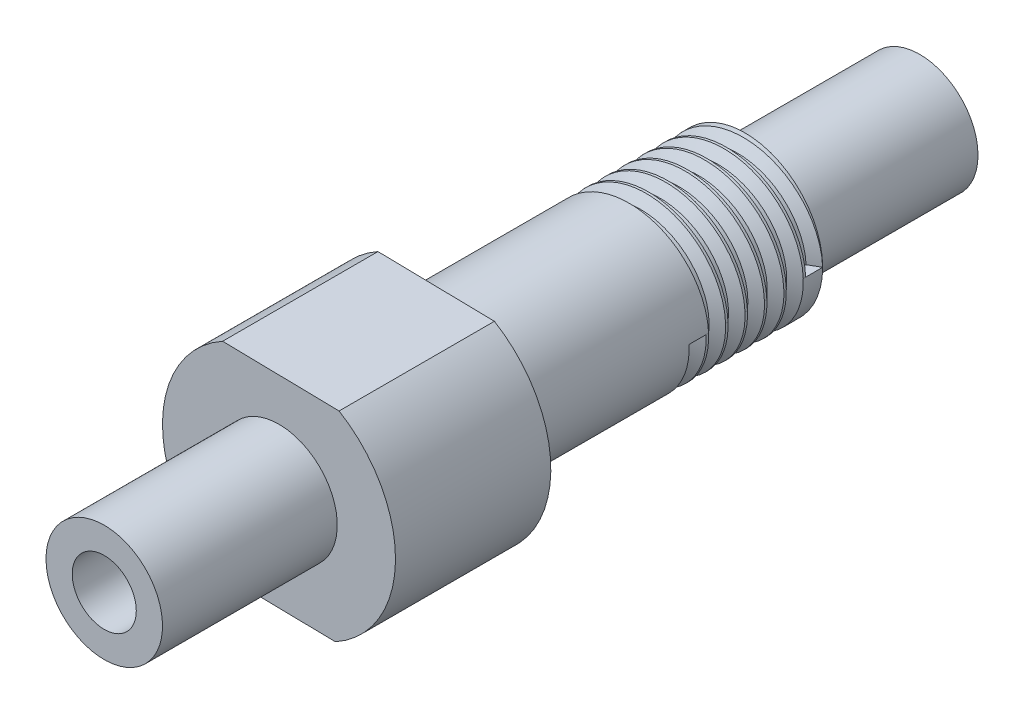
SolidWorks part; units mm, degrees
material "Stainless Steel (ferritic)"
ref_plane "Front Plane" through (0, 0, 0) normal (0, 0, 1) x (1, 0, 0)
ref_plane "Top Plane" through (0, 0, 0) normal (0, 1, 0) x (1, 0, 0)
ref_plane "Right Plane" through (0, 0, 0) normal (1, 0, 0) x (0, 0, -1)
sketch "Sketch1" plane through (0, 0, 0) normal (0, 0, 1) x (1, 0, 0)
  circle A0 centre (0, 0) radius 4
  dimension "D1" = 8
extrude "Boss-Extrude1" add sketch "Sketch1" along normal blind 16
sketch "Sketch2" plane through (0, 0, 16) normal (0, 0, 1) x (1, 0, 0)
  circle A0 centre (0, 0) radius 6
  dimension "D1" = 12
extrude "Boss-Extrude2" add sketch "Sketch2" along normal blind 8
sketch "Sketch3" plane through (0, 0, 0) normal (0, 0, -1) x (-1, 0, 0)
  circle A0 centre (0, 0) radius 3
  dimension "D1" = 6
extrude "Boss-Extrude3" add sketch "Sketch3" along normal blind 9
sketch "Sketch8" plane through (0, 0, 24) normal (0, 0, 1) x (1, 0, 0)
  circle A0 centre (0, 0) radius 3
  dimension "D1" = 6
extrude "Boss-Extrude4" add sketch "Sketch8" along normal blind 9
hole_wizard "M4x0.7 Tapped Hole2" positions "Sketch12" profile "Sketch13" tap size "M4x0.7" standard "ANSI Metric"
sketch "Sketch12" plane through (0, 0, 33) normal (0, 0, 1) x (1, 0, 0)
  point P0 (0, 0)
sketch "Sketch13" plane through (0, 0, 33) normal (1, 0, 0) x (0, -1, 0)
  line L0 (0, 0) -> (0, 10.9914)
  line L1 (0, 10.9914) -> (1.65, 10)
  line L2 (1.65, 10) -> (1.65, 0)
  line L5 (1.65, 0) -> (0, 0)
  line L10 (0, 10.9914) -> (-1.65, 10) construction
  line L11 (0, -6.35) -> (0, 107.95) construction
  dimension "Tap Drill Dia." = 3.3
  dimension "Tap Drill Depth" = 10
  dimension "Drill Angle" = 118
cosmetic thread "Hole Thread2" parameters "D1"=5, "D2"=4
thread "Thread1" pitch 1 method cut profile "Thread Profile2" start angle 0, offset 0, length 6, pitch 1, diameter 8
ref_plane "Plane2" through (4, 0, 0) normal (0, -1, 0) x (1, 0, 0)
sketch "Thread Profile2" plane through (4, 0, 0) normal (0, -1, 0) x (1, 0, 0)
  line L0 (0, 0) -> (0, 1) construction
  line L11 (0, 0) -> (0, 0.875)
  line L12 (0, 0.875) -> (-0.5413, 0.5625)
  line L13 (-0.5413, 0.5625) -> (-0.5413, 0.3125)
  line L15 (-0.5413, 0.3125) -> (0, 0)
  line L17 (-0.5413, 0.4375) -> (0, 0.4375) construction
  point P2 (0, 0)
  dimension "Pitch" = 1
  dimension "Profile_Angle" = 60
  dimension "Profile_Land" = 0.25
  dimension "Profile_Height" = 0.5413
hole_wizard "M4x0.7 Tapped Hole3" positions "Sketch32" profile "Sketch33" tap size "M4x0.7" standard "ANSI Metric"
sketch "Sketch32" plane through (0, 0, -9) normal (0, 0, -1) x (-1, 0, 0)
  point P0 (0, 0)
cosmetic thread "Hole Thread3" parameters "D1"=42, "D2"=4
sketch "Sketch33" plane through (0, 0, -9) normal (1, 0, 0) x (0, 1, 0)
  line L0 (0, 0) -> (0, 10.9914)
  line L1 (0, 10.9914) -> (1.65, 10)
  line L2 (1.65, 10) -> (1.65, 0)
  line L5 (1.65, 0) -> (0, 0)
  line L10 (0, 10.9914) -> (-1.65, 10) construction
  line L11 (0, -6.35) -> (0, 107.95) construction
  dimension "Tap Drill Dia." = 3.3
  dimension "Tap Drill Depth" = 10
  dimension "Drill Angle" = 118
sketch "Sketch36" plane through (0, 0, 24) normal (0, 0, 1) x (1, 0, 0)
  line L1 (3.0947, 5.1403) -> (-2.9043, 5.2502)
  line L2 (-2.9043, 5.2502) -> (-5.999, 0.1099)
  line L3 (-5.999, 0.1099) -> (-3.0947, -5.1403)
  line L4 (-3.0947, -5.1403) -> (2.9043, -5.2502)
  line L5 (2.9043, -5.2502) -> (5.999, -0.1099)
  line L6 (5.999, -0.1099) -> (3.0947, 5.1403)
  circle A0 centre (0, 0) radius 5.1962 construction
  circle A1 centre (0, 0) radius 6
  circle M2 centre (0, 0) radius 6
extrude "Cut-Extrude1" cut sketch "Sketch36" against normal blind 10 contours L1 M2 | L4 M2 region at (0.1011, 5.5187, 24) region at (-0.1011, -5.5187, 24)
